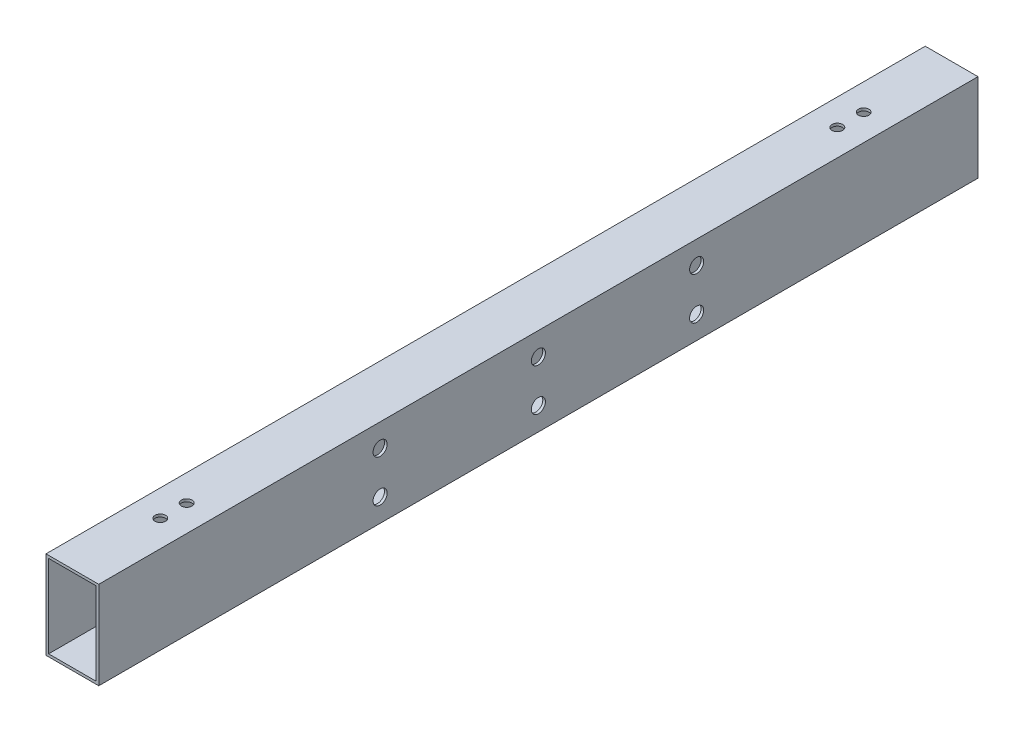
SolidWorks part; units mm, degrees
ref_plane "Płaszczyzna przednia" through (0, 0, 0) normal (0, 0, 1) x (1, 0, 0)
ref_plane "Płaszczyzna górna" through (0, 0, 0) normal (0, 1, 0) x (1, 0, 0)
ref_plane "Płaszczyzna prawa" through (0, 0, 0) normal (1, 0, 0) x (0, 0, -1)
sketch "Szkic1" plane through (0, 0, 0) normal (0, 0, 1) x (1, 0, 0)
  line L1 (0, 0) -> (30, 0)
  line L2 (0, 0) -> (0, 50)
  line L3 (0, 50) -> (30, 50)
  line L4 (30, 0) -> (30, 50)
  dimension "D1" = 50
  dimension "D2" = 30
sketch "Szkic2" plane through (0, 0, 0) normal (0, 0, 1) x (1, 0, 0)
  line L0 (30, 0) -> (30, 50) construction
  line L1 (1.5, 48.5) -> (28.5, 48.5)
  line L2 (1.5, 48.5) -> (1.5, 1.5)
  line L3 (1.5, 1.5) -> (28.5, 1.5)
  line L4 (28.5, 48.5) -> (28.5, 1.5)
  line L5 (0, 0) -> (0, 50) construction
  line L6 (0, 50) -> (30, 50) construction
  line L7 (0, 0) -> (30, 0) construction
  dimension "D1" = 1.5
  dimension "D2" = 1.5
  dimension "D3" = 1.5
  dimension "1,5" = 1.5
extrude "Dodanie-wyciągnięcie1" add sketch "Szkic1" along normal blind 500 contours L4 L3 L2 L1
extrude "Wytnij-wyciągnięcie7" cut sketch "Szkic2" along normal through all
sketch "Szkic5" plane through (0, 0, 0) normal (0, 1, 0) x (1, 0, 0)
  line L0 (0, -500) -> (0, 0) construction
  line L1 (0, -500) -> (30, -500) construction
  line L2 (0, 0) -> (30, 0) construction
  circle A0 centre (15, -450) radius 3
  circle A1 centre (15, -435) radius 3
  circle A2 centre (15, -50) radius 3
  circle A3 centre (15, -65) radius 3
  dimension "D1" = 6
  dimension "D2" = 15
  dimension "D3" = 50
  dimension "D4" = 6
  dimension "D5" = 15
  dimension "D6" = 15
  dimension "D7" = 6
  dimension "D8" = 15
  dimension "D9" = 50
  dimension "D10" = 6
  dimension "D11" = 15
  dimension "D12" = 15
extrude "Wytnij-wyciągnięcie13" cut sketch "Szkic5" along normal through all contours A3 | A2 | A1 | A0
sketch "Szkic6" plane through (30, 0, 0) normal (1, 0, 0) x (0, 0, -1)
  line L0 (-500, 25) -> (0, 25) construction
  line L1 (-500, 0) -> (-500, 50) construction
  line L2 (0, 0) -> (0, 50) construction
  line L3 (-250, 50) -> (-250, 0) construction
  line L4 (-500, 50) -> (0, 50) construction
  line L5 (16.5, 0) -> (-16.5, 0) construction
  circle A0 centre (-250, 37) radius 4
  circle A1 centre (-250, 13) radius 4
  circle A2 centre (-340, 13) radius 4
  circle A3 centre (-340, 37) radius 4
  circle A4 centre (-160, 13) radius 4
  circle A5 centre (-160, 37) radius 4
  dimension "D1" = 8
  dimension "D2" = 8
  dimension "D5" = 8
  dimension "D6" = 8
  dimension "D7" = 24
  dimension "D8" = 90
  dimension "D9" = 13
  dimension "D10" = 90
  dimension "D3" = 13
  dimension "D4" = 13
extrude "Wytnij-wyciągnięcie14" cut sketch "Szkic6" against normal through all
